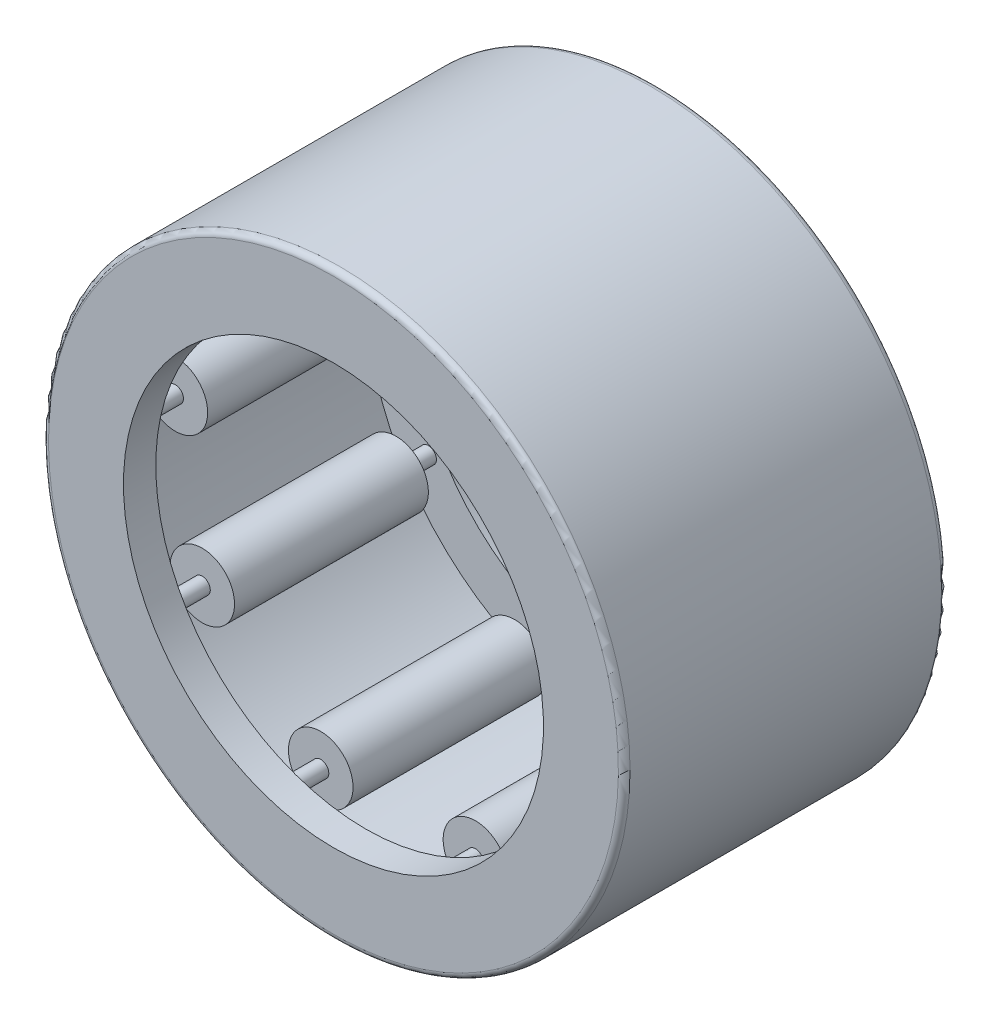
SolidWorks part; units mm, degrees
ref_plane "Front Plane" through (0, 0, 0) normal (0, 0, 1) x (1, 0, 0)
ref_plane "Top Plane" through (0, 0, 0) normal (0, 1, 0) x (1, 0, 0)
ref_plane "Right Plane" through (0, 0, 0) normal (1, 0, 0) x (0, 0, -1)
sketch "Sketch1" plane through (0, 0, 0) normal (1, 0, 0) x (0, 0, -1)
  line L0 (-3.9687, 0) -> (3.9688, 0) construction
  line L1 (0, 0) -> (0, 7.1438) construction
  line L2 (-3.9687, 0) -> (-3.9687, 7.1437) construction
  line L3 (-3.9687, 7.1437) -> (3.9687, 7.1437)
  line L4 (3.9687, 7.1437) -> (3.9688, 0) construction
  line L5 (3.9688, 0) -> (3.175, 0) construction
  line L6 (3.175, 0) -> (3.175, 6.35) construction
  line L7 (3.175, 6.35) -> (-3.175, 6.35)
  line L8 (-3.175, 6.35) -> (-3.175, 0) construction
  line L9 (-3.175, 0) -> (-3.9687, 0) construction
  line L10 (-3.9687, 7.1437) -> (-3.9687, 5.1594)
  line L11 (-3.9687, 5.1594) -> (-3.175, 5.1594)
  line L12 (-3.175, 5.1594) -> (-3.175, 6.35)
  line L13 (3.175, 7.1437) -> (3.175, 6.35) construction
  line L14 (3.175, 6.35) -> (3.175, 5.1594)
  line L15 (3.175, 5.1594) -> (3.9687, 5.1594)
  line L16 (3.9687, 5.1594) -> (3.9687, 7.1437)
  line L17 (3.175, 6.35) -> (3.175, 5.5563) construction
  line L18 (3.175, 5.5563) -> (3.175, 4.7625) construction
  point P5 (0, 4.7625)
  dimension "Width" = 7.9375
  dimension "OD" = 14.2875
  dimension "Shaft Dia" = 9.525
revolve "Revolve1" add sketch "Sketch1" angle 360 about L0
sketch "Sketch2" plane through (0, 0, 0) normal (1, 0, 0) x (0, 0, -1)
  line L0 (3.175, 6.35) -> (-3.175, 6.35) construction
  line L1 (-2.3812, 5.5562) -> (2.3812, 5.5563) construction
  line L2 (-2.3812, 5.5562) -> (-2.3812, 6.35) construction
  line L3 (-2.3812, 6.35) -> (2.3812, 6.35)
  line L4 (2.3812, 5.5563) -> (2.3812, 6.35) construction
  line L5 (3.175, 5.1594) -> (3.9687, 5.1594) construction
  line L6 (-3.175, 5.5563) -> (-2.3812, 5.5562) construction
  line L7 (2.3812, 5.5563) -> (3.175, 5.5563) construction
  line L8 (-3.9687, 5.1594) -> (-3.175, 5.1594) construction
  line L9 (-2.3812, 5.7547) -> (-2.3812, 5.3578) construction
  line L10 (-3.175, 5.5563) -> (-3.175, 5.1594) construction
  line L11 (-2.3812, 6.35) -> (-2.3812, 5.7547)
  line L12 (2.3812, 6.35) -> (2.3812, 5.7547)
  line L13 (2.3812, 5.7547) -> (-2.3812, 5.7547)
  line L14 (0, 6.35) -> (0, 4.7625) construction
  line L15 (-3.175, 5.1594) -> (-3.175, 6.35) construction
  line L16 (-2.3812, 5.3578) -> (-3.175, 5.3578) construction
  line L17 (0, 0) -> (3.9687, 0) construction
  line L31 (3.9687, -7.1438) -> (3.9687, 7.1437) construction
  point P16 (0, 5.5562)
revolve "Revolve2" add sketch "Sketch2" angle 360 about L1
sketch "Sketch3" plane through (0, 0, 0) normal (1, 0, 0) x (0, 0, -1)
  line L0 (3.175, 6.35) -> (3.175, 5.1594) construction
  line L1 (-3.175, 5.5563) -> (3.175, 5.5563)
  line L2 (-3.175, 5.5563) -> (-3.175, 5.7547)
  line L3 (-3.175, 5.7547) -> (3.175, 5.7547)
  line L4 (3.175, 5.5563) -> (3.175, 5.7547)
  line L5 (0, 0) -> (3.9687, 0) construction
  line L6 (3.9687, -7.1438) -> (3.9687, 7.1437) construction
revolve "Revolve3" add sketch "Sketch3" angle 360 about L1
ref_axis "Axis1" through (0, 0, -3.9688) along (0, 0, 1)
pattern_circular "CirPattern1" count 9 every 40 about axis through (0, 0, -3.9688) along (0, 0, 1) of bodies 166 167
fillet "Fillet1" radius 0.1429 2 edges at (0, -7.1438, -3.9687) (0, -7.1438, 3.9687)
sketch "Sketch4" plane through (0, 0, 0) normal (1, 0, 0) x (0, 0, -1)
  line L1 (3.8259, 4.7625) -> (2.3812, 4.7625)
  line L2 (3.8259, 4.7625) -> (3.8259, 5.1594)
  line L3 (3.8259, 5.1594) -> (2.3812, 5.1594)
  line L4 (2.3812, 4.7625) -> (2.3812, 5.1594)
  line L5 (-3.9687, 5.1594) -> (-3.175, 5.1594) construction
  line L6 (3.8259, -7.1438) -> (3.8259, 7.1437) construction
  line L7 (2.3812, 6.35) -> (2.3812, 5.7547) construction
revolve "Revolve4" [suppressed] add sketch "Sketch4" angle 360 about L0
sketch "Sketch5" plane through (0, 0, 0) normal (1, 0, 0) x (0, 0, -1)
  line L0 (-3.8259, 7.1437) -> (-3.8259, -7.1438) construction
  line L1 (-2.3812, 4.7625) -> (-3.8259, 4.7625)
  line L2 (-2.3812, 4.7625) -> (-2.3812, 5.1594)
  line L3 (-2.3812, 5.1594) -> (-3.8259, 5.1594)
  line L4 (-3.8259, 4.7625) -> (-3.8259, 5.1594)
  line L6 (-2.3812, 6.35) -> (-2.3812, 5.7547) construction
  line L7 (-3.9687, 5.1594) -> (-3.175, 5.1594) construction
revolve "Revolve5" [suppressed] add sketch "Sketch5" angle 360 about L0
sketch "Front View" plane through (0, 0, 0) normal (0, 0, 1) x (1, 0, 0)
  circle A0 centre (0, 0) radius 4.7625 construction
  circle A1 centre (0, 0) radius 7.1438 construction
  dimension "OD" = 14.2875
  dimension "ID" = 9.525
sketch "Right View" plane through (0, 0, 0) normal (1, 0, 0) x (0, 0, -1)
  line L0 (-3.9688, 7.1438) -> (3.9688, 7.1438) construction
  dimension "Width" = 7.9375
ref_axis "Center Axis 1" through (0, 0, -3.8259) along (0, 0, 1)
ref_plane "Contact Plane 1" through (0, 0, 3.9687) normal (0, 0, 1) x (1, 0, 0)
ref_plane "Contact Plane 2" through (0, 0, -3.9687) normal (0, 0, -1) x (-1, 0, 0)
equation "\"Rollers@CirPattern1\" = \"OD@Sketch1\"*16"
equation "\"D1@Fillet1\" = \"OD@Sketch1\"*.01"
equation "\"Angle@CirPattern1\"= 360 / \"Rollers@CirPattern1\""
equation "\"OD@Front View\"=\"OD@Sketch1\""
equation "\"ID@Front View\"=\"Shaft Dia@Sketch1\""
equation "\"Width@Right View\"=\"Width@Sketch1\""
